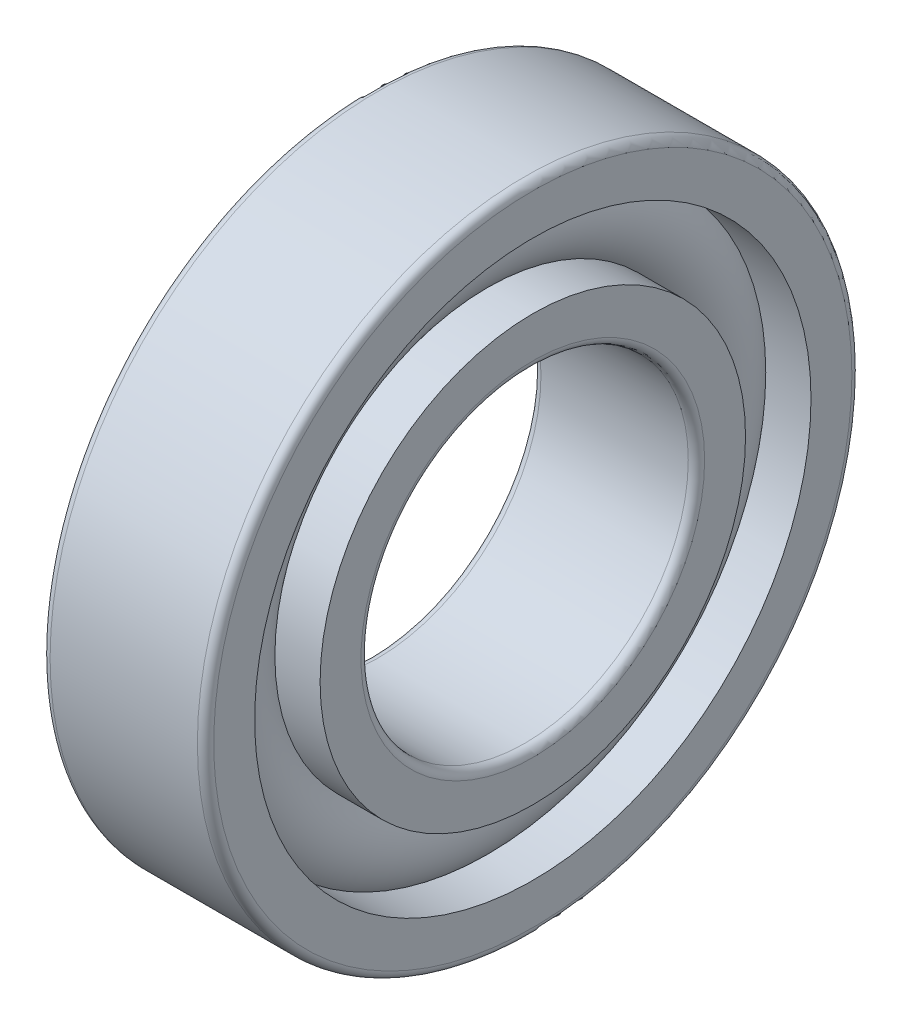
SolidWorks part; units mm, degrees
ref_plane "Plane1" through (0, 0, 0) normal (0, 0, 1) x (1, 0, 0)
ref_plane "Plane2" through (0, 0, 0) normal (0, 1, 0) x (1, 0, 0)
ref_plane "Plane3" through (0, 0, 0) normal (1, 0, 0) x (0, 0, -1)
sketch "Clipboard" plane through (0, 0, 0) normal (0, 0, 1) x (1, 0, 0)
  line L0 (-10, 0) -> (10, 0) construction
  line L1 (0, 0) -> (22.3471, -0.7804)
  line L2 (0, 0) -> (5.9963, 0.2094)
  line L3 (0, 0) -> (22.3471, -0.7804)
  line L4 (0, 0) -> (-22.3573, -0.3902)
sketch "CagSpiSke" plane through (0, 0, 0) normal (0, 0, 1) x (1, 0, 0)
  line L0 (0.12, 5.8) -> (0.12, 6.2)
  line L1 (0.12, 6.2) -> (-0.12, 6.2)
  line L2 (-0.12, 6.2) -> (-0.12, 5.8)
  line L3 (-0.12, 5.8) -> (0.12, 5.8)
  line L4 (-20.6375, 0) -> (20.6375, 0) construction
  line L5 (0, 0) -> (0, 23.7692) construction
revolve "CageSpine" add sketch "CagSpiSke" angle 0.001 about L4 reverse direction yes
ref_axis "Axis1" through (-50, 0, 0) along (1, 0, 0)
sketch "CagBalSke" plane through (0, 0, 0) normal (0, 0, 1) x (1, 0, 0)
  line L0 (-1.32, 6) -> (1.32, 6)
  line L1 (-1.905, 6) -> (1.905, 6) construction
  line L2 (-10, 0) -> (10, 0) construction
  line L3 (0, 0) -> (0, 24) construction
  arc A0 (1.32, 6) -> (-1.32, 6) centre (0, 6) cw
revolve "CageBall" [suppressed] add sketch "CagBalSke" angle 360 about L1 reverse direction yes
pattern_circular "CageBalls" [suppressed] count 2 every 180 about axis through (-50, 0, 0) along (1, 0, 0)
sketch "CagTrmODSke" plane through (0, 0, 0) normal (0, 0, 1) x (1, 0, 0)
  line L0 (1.321, 6.2) -> (1.321, 7.321)
  line L1 (1.321, 7.321) -> (-1.321, 7.321)
  line L2 (-1.321, 7.321) -> (-1.321, 6.2)
  line L3 (-1.321, 6.2) -> (1.321, 6.2)
  line L4 (-20.6375, 0) -> (20.6375, 0) construction
  line L5 (0, 0) -> (0, 25) construction
revolve "CageTrimOD" [suppressed] cut sketch "CagTrmODSke" angle 360 about L4 reverse direction yes
sketch "CagTrmIDSke" plane through (0, 0, 0) normal (0, 0, 1) x (1, 0, 0)
  line L0 (1.321, 4.681) -> (1.321, 5.8)
  line L1 (1.321, 5.8) -> (-1.321, 5.8)
  line L2 (-1.321, 5.8) -> (-1.321, 4.681)
  line L3 (-1.321, 4.681) -> (1.321, 4.681)
  line L4 (-20.6375, 0) -> (20.6375, 0) construction
  line L5 (0, 0) -> (0, 25) construction
revolve "CageTrimID" [suppressed] cut sketch "CagTrmIDSke" angle 360 about L4 reverse direction yes
sketch "BalSimSke" plane through (0, 0, 0) normal (0, 0, 1) x (1, 0, 0)
  line L0 (-10, 0) -> (10, 0) construction
  line L1 (-10, 6) -> (10, 6) construction
  line L2 (0, 0) -> (0, 23) construction
  circle A0 centre (0, 6) radius 1.2
revolve "BallsSimplified" add sketch "BalSimSke" angle 360 about L0
sketch "BalDetSke" plane through (0, 0, 0) normal (0, 0, 1) x (1, 0, 0)
  line L0 (-1.2, 6) -> (1.2, 6)
  line L1 (-1.905, 6) -> (1.905, 6) construction
  line L2 (0, 0) -> (0, 25) construction
  arc A0 (1.2, 6) -> (-1.2, 6) centre (0, 6) cw
revolve "BallDetailed" [suppressed] add sketch "BalDetSke" angle 360 about L1 reverse direction yes
sketch "InnRacSke" plane through (0, 0, 0) normal (0, 0, 1) x (1, 0, 0)
  line L0 (-0.8606, 5.2) -> (-2, 5.2)
  line L1 (-2, 5.2) -> (-2, 4.2)
  line L2 (-1.8, 4) -> (1.8, 4)
  line L3 (2, 4.2) -> (2, 5.2)
  line L4 (2, 5.2) -> (0.8606, 5.2)
  line L5 (-20.6375, 0) -> (20.6375, 0) construction
  line L6 (0, 0) -> (0, 30) construction
  arc A0 (-2, 4.2) -> (-1.8, 4) centre (-1.8, 4.2) ccw
  arc A1 (1.8, 4) -> (2, 4.2) centre (1.8, 4.2) ccw
  arc A2 (0.8606, 5.2) -> (-0.8606, 5.2) centre (0, 6) cw
revolve "InnerRace" add sketch "InnRacSke" angle 360 about L5 reverse direction yes
sketch "OutRacSke" plane through (0, 0, 0) normal (0, 0, 1) x (1, 0, 0)
  line L0 (-0.8606, 6.8) -> (-2, 6.8)
  line L1 (-2, 6.8) -> (-2, 7.8)
  line L2 (-1.8, 8) -> (1.8, 8)
  line L3 (2, 7.8) -> (2, 6.8)
  line L4 (2, 6.8) -> (0.8606, 6.8)
  line L5 (-20.6375, 0) -> (20.6375, 0) construction
  line L6 (0, 0) -> (0, 30) construction
  arc A0 (-2, 7.8) -> (-1.8, 8) centre (-1.8, 7.8) cw
  arc A1 (1.8, 8) -> (2, 7.8) centre (1.8, 7.8) cw
  arc A2 (0.8606, 6.8) -> (-0.8606, 6.8) centre (0, 6) ccw
revolve "OuterRace" add sketch "OutRacSke" angle 360 about L5 reverse direction yes
pattern_circular "BallsDetailed" [suppressed] count 2 every 180 about axis through (-50, 0, 0) along (1, 0, 0)
equation "\"BallCLRad@Clipboard\" = ( \"OD@OutRacSke\" + \"ID@InnRacSke\" ) / 4"
equation "\"BallCLRad@BalSimSke\" = \"BallCLRad@Clipboard\""
equation "\"BallCLRad@BalDetSke\" = \"BallCLRad@Clipboard\""
equation "\"BallCLRad@InnRacSke\" = \"BallCLRad@Clipboard\""
equation "\"BallCLRad@OutRacSke\" = \"BallCLRad@Clipboard\""
equation "\"Ball_diameter@InnRacSke\" = \"Ball_diameter@BalDetSke\" - 0.05"
equation "\"Ball_diameter@OutRacSke\" = \"Ball_diameter@BalDetSke\" - 0.05"
equation "\"Ball_diameter@BalSimSke\" = \"Ball_diameter@BalDetSke\""
equation "\"Width@OutRacSke\" = \"Width@InnRacSke\""
equation "\"Fillet_radius@OutRacSke\" = \"Fillet_radius@InnRacSke\""
equation "\"Max_count@Clipboard\" = int( 3.14159265 / atn(( \"Ball_diameter@BalDetSke\" / 2) / sqr( \"BallCLRad@Clipboard\"  *  \"BallCLRad@Clipboard\" - ( \"Ball_diameter@BalDetSke\" / 2) *  ( \"Ball_diameter@BalDetSke\" / 2))))"
equation "\"Max_count@Clipboard\" = ((sgn( \"Max_count@Clipboard\" - \"Count@Clipboard\" )-1)*( \"Max_count@Clipboard\" - \"Count@Clipboard\" ))/-2+ \"Count@Clipboard\""
equation "\"Count@BallsDetailed\" = int( \"Show_count@Clipboard\" ) "
equation "\"Count@BallsDetailed\" = ((sgn( \"Count@BallsDetailed\" - \"Max_count@Clipboard\" )-1)*( \"Count@BallsDetailed\" - \"Max_count@Clipboard\" ))/-2+ \"Max_count@Clipboard\""
equation "\"Count@BallsDetailed\" = ((sgn( \"Count@BallsDetailed\" - \"Min_count@Clipboard\" )+1)*( \"Count@BallsDetailed\" - \"Min_count@Clipboard\"))/2 +\"Min_count@Clipboard\""
equation "\"Angle@BallsDetailed\" = 360.0 / \"Max_count@Clipboard\""
equation "\"BallCLRad@CagBalSke\" = \"BallCLRad@Clipboard\""
equation "\"Count@CageBalls\" = \"Count@BallsDetailed\""
equation "\"Angle@CageBalls\" = \"Angle@BallsDetailed\""
equation "\"Angle@CageSpine\" =  \"Angle@CageBalls\" * ( \"Count@CageBalls\" -1 + int( \"Count@CageBalls\" / \"Max_count@Clipboard\" ) )  + 0.001 -  int( \"Count@CageBalls\" / \"Max_count@Clipboard\" ) * 0.001"
equation "\"Angle@CageSpine\" =  \"Angle@CageSpine\" * int( \"Min_count@Clipboard\" / 2) + int(1 / \"Min_count@Clipboard\")  * 0.001"
equation "\"CageWallOD@CagBalSke\" =  \"Ball_diameter@BalDetSke\" * 1.1"
equation "\"Thickness@CagSpiSke\" =  \"Ball_diameter@BalDetSke\" * 0.1"
equation "\"OD@CagTrmODSke\" = \"BallCLRad@Clipboard\" * 2 + \"CageWallOD@CagBalSke\" + 0.002"
equation "\"ID@CagTrmODSke\" = \"BallCLRad@Clipboard\" * 2 + \"Ball_diameter@BalDetSke\" / 6"
equation "\"OD@CagTrmIDSke\" = \"BallCLRad@Clipboard\" * 2 - \"Ball_diameter@BalDetSke\" / 6"
equation "\"ID@CagTrmIDSke\" = \"BallCLRad@Clipboard\" * 2 - \"CageWallOD@CagBalSke\" + 0.002"
equation "\"OD@CagSpiSke\" = \"ID@CagTrmODSke\""
equation "\"ID@CagSpiSke\" = \"OD@CagTrmIDSke\""
equation "\"Width@CagTrmODSke\" = \"CageWallOD@CagBalSke\" + 0.002"
equation "\"Width@CagTrmIDSke\" = \"CageWallOD@CagBalSke\" + 0.002"
